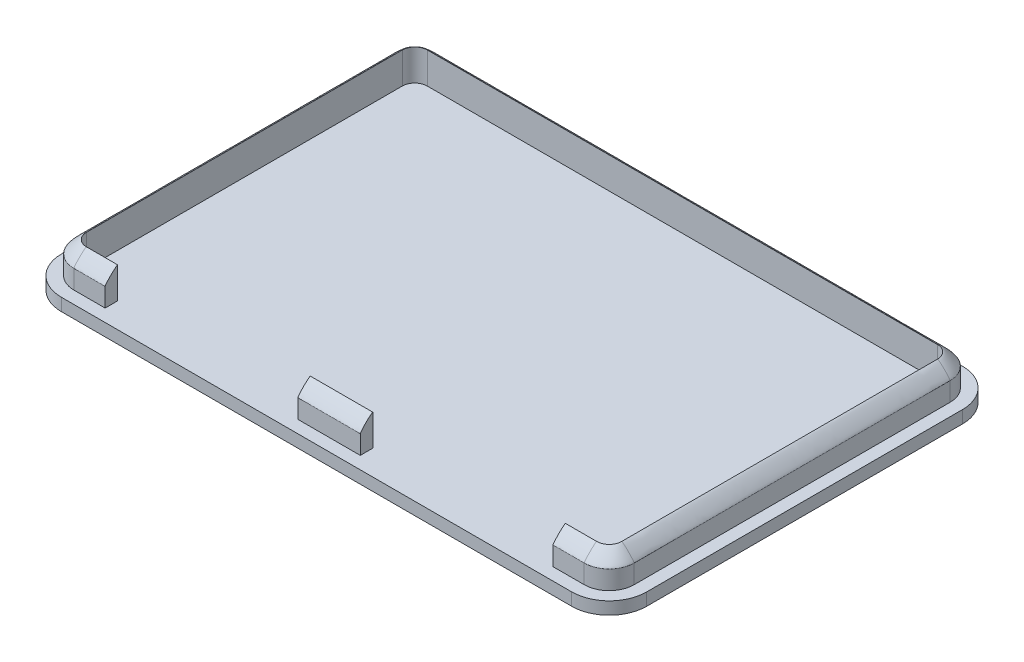
SolidWorks part; units mm, degrees
ref_plane "Alzado" through (0, 0, 0) normal (0, 0, 1) x (1, 0, 0)
ref_plane "Planta" through (0, 0, 0) normal (0, 1, 0) x (1, 0, 0)
ref_plane "Vista lateral" through (0, 0, 0) normal (1, 0, 0) x (0, 0, -1)
sketch "Croquis1" plane through (0, 0, 0) normal (0, 1, 0) x (1, 0, 0)
  line L1 (-40.87, -31.3) -> (40.87, -31.3)
  line L2 (-46.87, -25.3) -> (-46.87, 25.3)
  line L3 (-40.87, 31.3) -> (40.87, 31.3)
  line L4 (46.87, -25.3) -> (46.87, 25.3)
  line L5 (-46.87, -31.3) -> (46.87, 31.3) construction
  line L6 (-46.87, 31.3) -> (46.87, -31.3) construction
  arc A0 (40.87, -31.3) -> (46.87, -25.3) centre (40.87, -25.3) ccw
  arc A1 (40.87, 31.3) -> (46.87, 25.3) centre (40.87, 25.3) cw
  arc A2 (-46.87, 25.3) -> (-40.87, 31.3) centre (-40.87, 25.3) cw
  arc A3 (-40.87, -31.3) -> (-46.87, -25.3) centre (-40.87, -25.3) cw
  point P0 (0, 0)
  dimension "D3" = 6
  dimension "D1" = 62.6
  dimension "D2" = 93.74
extrude "Saliente-Extruir1" add sketch "Croquis1" along normal blind 2
sketch "Croquis2" plane through (0, 2, 0) normal (0, 1, 0) x (1, 0, 0)
  line L4 (42.87, -25.3) -> (42.87, 25.3)
  line L5 (40.87, 27.3) -> (-40.87, 27.3)
  line L6 (-42.87, 25.3) -> (-42.87, -25.3)
  line L7 (-40.87, -27.3) -> (40.87, -27.3)
  line L8 (44.87, -25.3) -> (44.87, 25.3)
  line L9 (40.87, 29.3) -> (-40.87, 29.3)
  line L10 (-44.87, 25.3) -> (-44.87, -25.3)
  line L11 (-40.87, -29.3) -> (40.87, -29.3)
  line L12 (44.87, -25.3) -> (44.87, 25.3)
  line L13 (40.87, 29.3) -> (-40.87, 29.3)
  line L14 (-44.87, 25.3) -> (-44.87, -25.3)
  line L15 (-40.87, -29.3) -> (40.87, -29.3)
  arc A4 (40.87, -27.3) -> (42.87, -25.3) centre (40.87, -25.3) ccw
  arc A5 (42.87, 25.3) -> (40.87, 27.3) centre (40.87, 25.3) ccw
  arc A6 (-40.87, 27.3) -> (-42.87, 25.3) centre (-40.87, 25.3) ccw
  arc A7 (-42.87, -25.3) -> (-40.87, -27.3) centre (-40.87, -25.3) ccw
  arc A8 (40.87, -29.3) -> (44.87, -25.3) centre (40.87, -25.3) ccw
  arc A9 (44.87, 25.3) -> (40.87, 29.3) centre (40.87, 25.3) ccw
  arc A10 (-40.87, 29.3) -> (-44.87, 25.3) centre (-40.87, 25.3) ccw
  arc A11 (-44.87, -25.3) -> (-40.87, -29.3) centre (-40.87, -25.3) ccw
  arc A12 (40.87, -29.3) -> (44.87, -25.3) centre (40.87, -25.3) ccw
  arc A13 (44.87, 25.3) -> (40.87, 29.3) centre (40.87, 25.3) ccw
  arc A14 (-40.87, 29.3) -> (-44.87, 25.3) centre (-40.87, 25.3) ccw
  arc A15 (-44.87, -25.3) -> (-40.87, -29.3) centre (-40.87, -25.3) ccw
  dimension "D1" = 2
  dimension "D2" = 2
extrude "Saliente-Extruir2" add sketch "Croquis2" along normal blind 5
fillet "Redondeo1" radius 2 8 edges at (0, 7, -29.3) (-43.6984, 7, -28.1284) (43.6984, 7, -28.1284) (-44.87, 7, 0) (44.87, 7, 0) (-43.6984, 7, 28.1284) (43.6984, 7, 28.1284) (0, 7, 29.3) conic rho 0.1
sketch "Croquis3" plane through (0, 2, 0) normal (0, 1, 0) x (1, 0, 0)
  line L0 (-40.87, -27.3) -> (40.87, -27.3) construction
  line L1 (-35.87, -27.3) -> (-5, -27.3)
  line L2 (-35.87, -27.3) -> (-35.87, -29.3)
  line L3 (-35.87, -29.3) -> (-5, -29.3)
  line L4 (-5, -27.3) -> (-5, -29.3)
  line L5 (40.87, -29.3) -> (-40.87, -29.3) construction
  line L6 (-40.87, -27.3) -> (40.87, -27.3) construction
  line L7 (5, -27.3) -> (35.87, -27.3)
  line L8 (5, -27.3) -> (5, -29.3)
  line L9 (5, -29.3) -> (35.87, -29.3)
  line L10 (35.87, -27.3) -> (35.87, -29.3)
  line L11 (0, 0) -> (0, -31.3) construction
  line L12 (-40.87, -31.3) -> (40.87, -31.3) construction
  line L13 (40.87, -27.3) -> (40.87, -29.3) construction
  line L14 (-40.87, -29.3) -> (-40.87, -27.3) construction
  dimension "D1" = 5
  dimension "D2" = 5
  dimension "D3" = 5
  dimension "D4" = 5
extrude "Cortar-Extruir1" cut sketch "Croquis3" along normal blind 8
